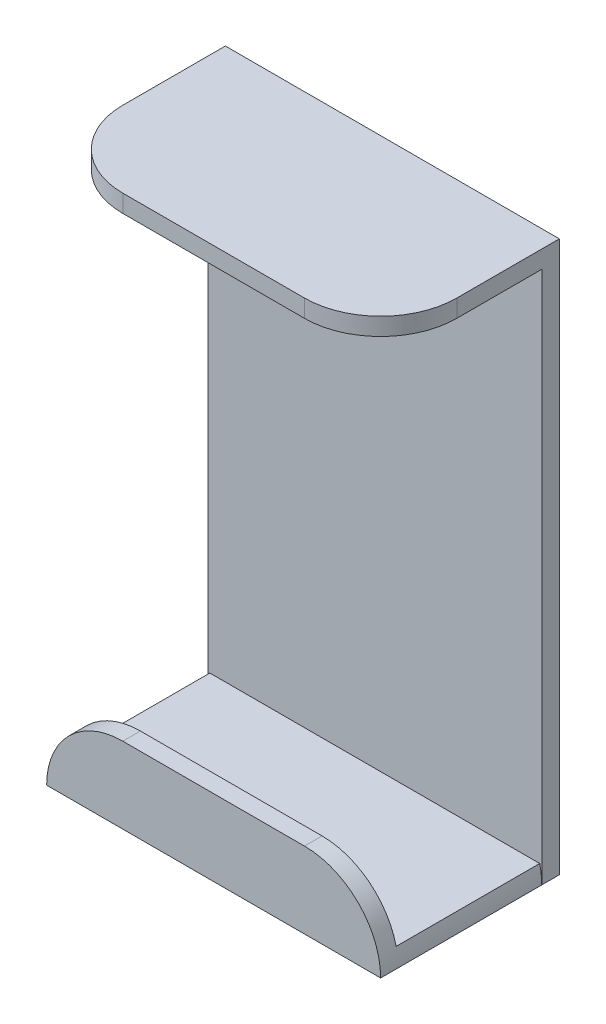
SolidWorks part; units mm, degrees
ref_plane "Front Plane" through (0, 0, 0) normal (0, 0, 1) x (1, 0, 0)
ref_plane "Top Plane" through (0, 0, 0) normal (0, 1, 0) x (1, 0, 0)
ref_plane "Right Plane" through (0, 0, 0) normal (1, 0, 0) x (0, 0, -1)
sketch "Sketch2" plane through (0, 0, 0) normal (0, 1, 0) x (1, 0, 0)
  line L0 (0, 0) -> (0, 33.5)
  line L1 (0, 33.5) -> (57, 33.5)
  line L2 (57, 33.5) -> (57, 0)
  line L3 (57, 0) -> (0, 0)
  dimension "D1" = 57
  dimension "D2" = 33.5
extrude "Boss-Extrude1" add sketch "Sketch2" along normal blind 100
sketch "Sketch3" plane through (57, 0, 0) normal (1, 0, 0) x (0, 0, -1)
  line L0 (0, 97) -> (30.5, 97)
  line L1 (0, 100) -> (0, 0) construction
  line L2 (30.5, 97) -> (30.5, 3)
  line L3 (30.5, 3) -> (0, 3)
  line L4 (0, 0) -> (33.5, 0) construction
  line L5 (33.5, 100) -> (33.5, 0) construction
  line L6 (0, 100) -> (33.5, 100) construction
  dimension "D1" = 3
  dimension "D2" = 3
  dimension "D3" = 3
extrude "Cut-Extrude3" cut sketch "Sketch3" against normal through all and the other way through all
sketch "Sketch4" plane through (57, 0, 0) normal (1, 0, 0) x (0, 0, -1)
  line L0 (0, 94) -> (27.5, 94)
  line L1 (0, 97) -> (0, 3) construction
  line L2 (27.5, 94) -> (27.5, 6)
  line L3 (27.5, 6) -> (3, 6)
  line L4 (3, 6) -> (3, 16)
  line L5 (3, 16) -> (0, 16)
  line L6 (0, 94) -> (0, 16)
  line L7 (0, 97) -> (30.5, 97) construction
  line L8 (30.5, 97) -> (30.5, 3) construction
  line L9 (30.5, 3) -> (0, 3) construction
  dimension "D1" = 3
  dimension "D2" = 3
  dimension "D3" = 3
  dimension "D4" = 3
  dimension "D5" = 13
extrude "Cut-Extrude5" cut sketch "Sketch4" against normal blind 100
fillet "Fillet2" radius 13 4 edges at (0, 95.5, 0) (57, 95.5, 0) (57, 16, -1.5) (0, 16, -1.5)
